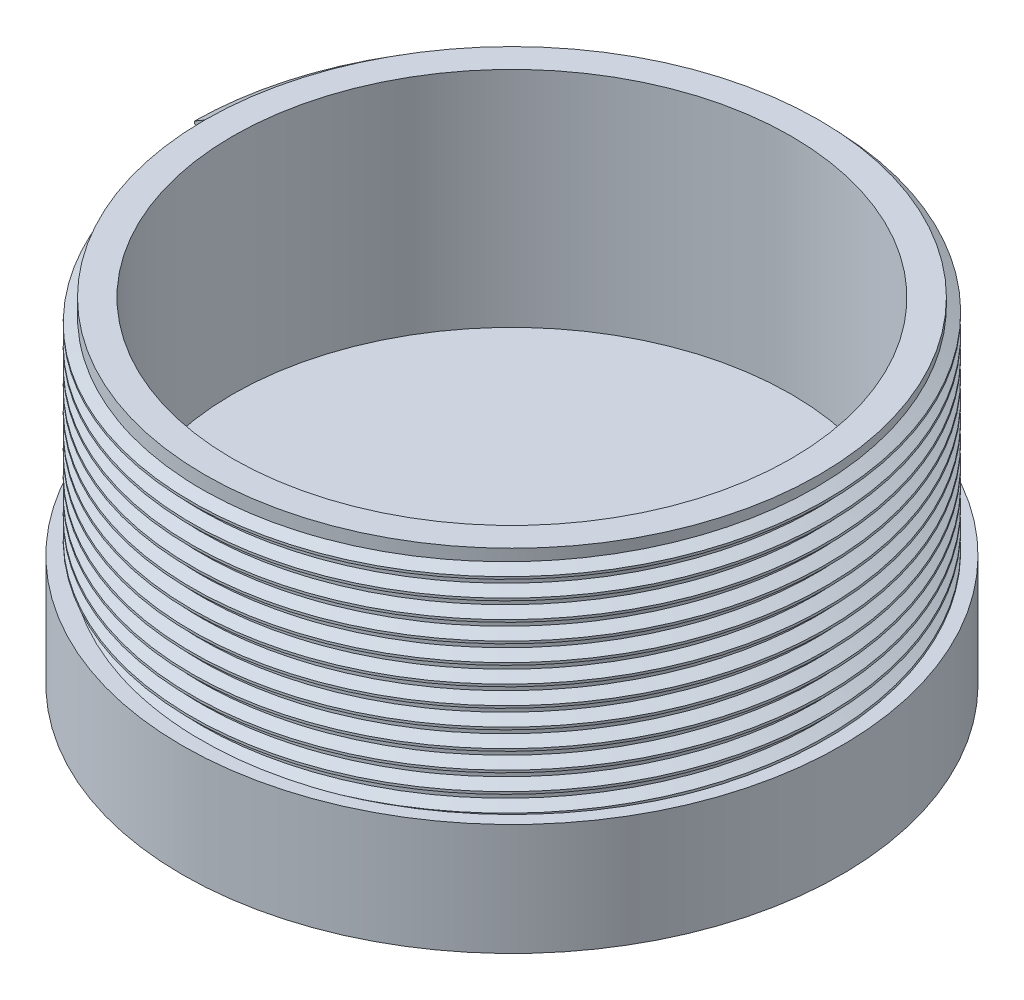
SolidWorks part; units mm, degrees
ref_plane "Front Plane" through (0, 0, 0) normal (0, 0, 1) x (1, 0, 0)
ref_plane "Top Plane" through (0, 0, 0) normal (0, 1, 0) x (1, 0, 0)
ref_plane "Right Plane" through (0, 0, 0) normal (1, 0, 0) x (0, 0, -1)
sketch "Sketch1" plane through (0, 0, 0) normal (0, 1, 0) x (1, 0, 0)
  circle A1 centre (0, 0) radius 37.465 construction
  circle A2 centre (0, 0) radius 37.465
extrude "Boss-Extrude1" add sketch "Sketch1" along normal blind 12.7
sketch "Sketch2" plane through (0, 12.7, 0) normal (0, 1, 0) x (1, 0, 0)
  circle A2 centre (0, 0) radius 34.925
  circle A3 centre (0, 0) radius 34.925
  dimension "D1" = 0
extrude "Boss-Extrude2" add sketch "Sketch2" along normal blind 25.4
thread "Thread1" pitch 2.1167 method extrude profile "Thread Profile1" start angle 0, offset 0, length 25.24, pitch 2.1167, diameter 69.85
ref_plane "Plane1" through (-34.925, 38.1, 0) normal (0, 0, 1) x (-1, 0, 0)
sketch "Thread Profile1" plane through (-34.925, 38.1, 0) normal (0, 0, 1) x (-1, 0, 0)
  line L0 (0, 0) -> (0, 2.1167) construction
  line L1 (0, 0) -> (1.1457, 0.6615)
  line L2 (1.1457, 0.6615) -> (1.1457, 0.926)
  line L3 (1.1457, 0.926) -> (0, 1.5875)
  line L4 (1.1457, 0.7937) -> (0, 0.7937) construction
  line L11 (0, 0) -> (0, 1.5875)
  point P2 (0, 0)
  dimension "Pitch" = 2.1167
  dimension "Profile_Angle" = 60
  dimension "Profile_Land" = 0.2646
  dimension "Profile_Height" = 1.1457
sketch "Sketch7" plane through (0, 38.1, 0) normal (0, 1, 0) x (1, 0, 0)
  circle A0 centre (0, 0) radius 31.75
  dimension "D1" = 63.5
extrude "Cut-Extrude1" cut sketch "Sketch7" against normal blind 25.4
